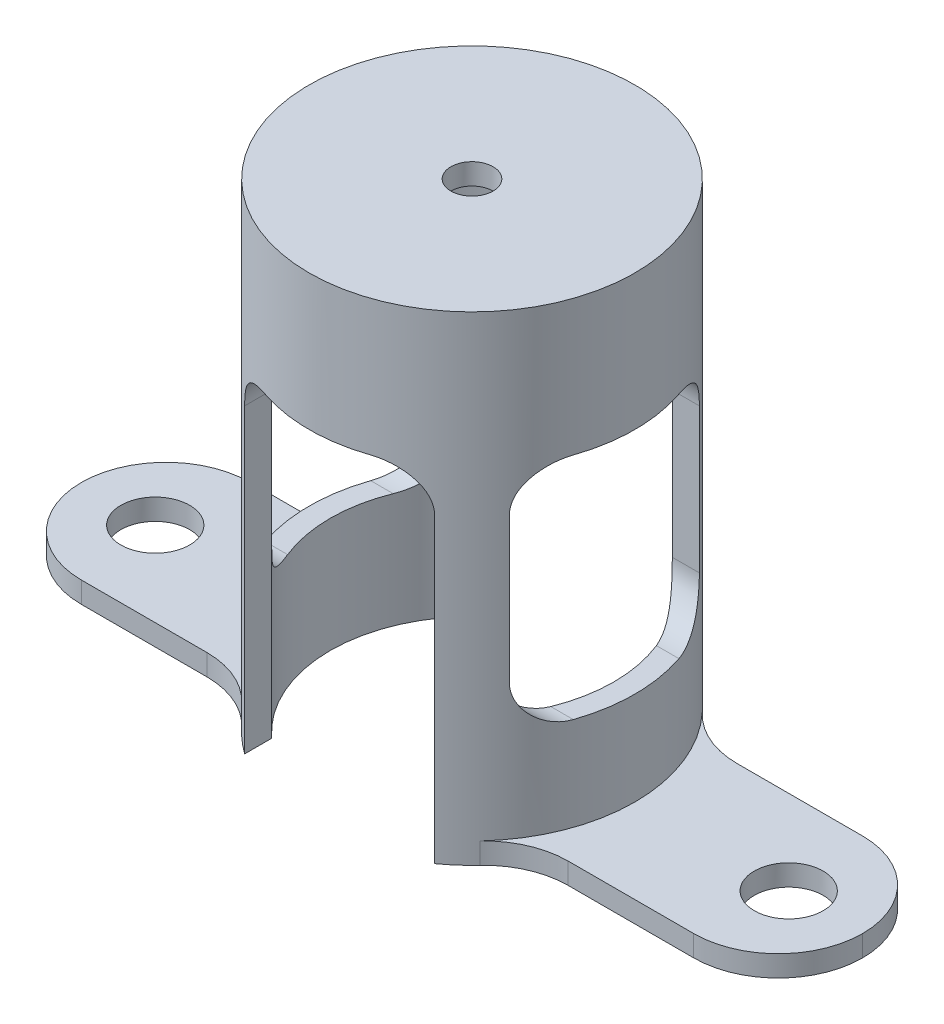
SolidWorks part; units mm, degrees
material "6061-T6 (SS)"
ref_plane "Front Plane" through (0, 0, 0) normal (0, 0, 1) x (1, 0, 0)
ref_plane "Top Plane" through (0, 0, 0) normal (0, 1, 0) x (1, 0, 0)
ref_plane "Right Plane" through (0, 0, 0) normal (1, 0, 0) x (0, 0, -1)
sketch "Sketch2" plane through (0, 0, 0) normal (0, 1, 0) x (1, 0, 0)
  circle A1 centre (0, 0) radius 7.715
  dimension "D2" = 15.43
extrude "Boss-Extrude1" add sketch "Sketch2" along normal blind 21.7
sketch "Sketch4" plane through (0, 21.7, 0) normal (0, 1, 0) x (1, 0, 0)
  circle A0 centre (0, 0) radius 1
  dimension "D1" = 2
extrude "Cut-Extrude2" cut sketch "Sketch4" against normal through all
sketch "Sketch11" plane through (0, 0, 0) normal (0, -1, 0) x (1, 0, 0)
  line L0 (6.5971, 4) -> (18.5, 4)
  line L1 (-18.5, 4) -> (-6.5971, 4)
  line L2 (-18.5, 4) -> (-18.5, -4)
  line L3 (-18.5, -4) -> (-6.5971, -4)
  line L4 (18.5, 4) -> (18.5, -4)
  line L5 (-18.5, 4) -> (18.5, -4) construction
  line L6 (-18.5, -4) -> (18.5, 4) construction
  line L7 (6.5971, -4) -> (18.5, -4)
  arc A0 (6.5971, 4) -> (-6.5971, 4) centre (0, 0) ccw
  circle A1 centre (0, 0) radius 6.715
  arc A2 (-6.5971, -4) -> (6.5971, -4) centre (0, 0) ccw
  point P0 (0, 0)
  dimension "D3" = 15.43
  dimension "D4" = 13.43
  dimension "D1" = 8
  dimension "D2" = 37
extrude "Boss-Extrude2" add sketch "Sketch11" along normal blind 1
sketch "Sketch12" plane through (0, 0, 0) normal (0, -1, 0) x (1, 0, 0)
  circle A0 centre (0, 0) radius 6.715
  dimension "D1" = 13.43
extrude "Cut-Extrude7" cut sketch "Sketch12" against normal blind 20.7
ref_plane "Plane4" through (0, 0, 30) normal (0, 0, 1) x (1, 0, 0)
sketch "Sketch13" plane through (0, 0, 30) normal (0, 0, 1) x (1, 0, 0)
  line L0 (0, -8.4865) -> (0, 8.4865) construction
  line L1 (-4.5, 15.275) -> (4.5, 15.275)
  line L2 (-4.5, 15.275) -> (-4.5, -1)
  line L3 (-4.5, -1) -> (4.5, -1)
  line L4 (4.5, 15.275) -> (4.5, -1)
  line L5 (-4.5, 15.275) -> (4.5, -1) construction
  line L6 (-4.5, -1) -> (4.5, 15.275) construction
  line L7 (-6.5971, -1) -> (6.5971, -1) construction
  point P0 (0, 7.1375)
  dimension "D1" = 16.275
  dimension "D2" = 9
extrude "Cut-Extrude8" cut sketch "Sketch13" against normal through all
ref_plane "Plane5" through (30, 0, 0) normal (1, 0, 0) x (0, 0, -1)
sketch "Sketch14" plane through (30, 0, 0) normal (1, 0, 0) x (0, 0, -1)
  line L0 (0, 13.585) -> (0, -13.585) construction
  line L1 (-4.5, 15.275) -> (4.5, 15.275)
  line L2 (-4.5, 15.275) -> (-4.5, 4.425)
  line L3 (-4.5, 4.425) -> (4.5, 4.425)
  line L4 (4.5, 15.275) -> (4.5, 4.425)
  line L5 (-4.5, 15.275) -> (4.5, 4.425) construction
  line L6 (-4.5, 4.425) -> (4.5, 15.275) construction
  line L7 (4, -1) -> (-4, -1) construction
  point P0 (0, 9.85)
  dimension "D2" = 9
  dimension "D1" = 10.85
  dimension "D3" = 10.85
extrude "Cut-Extrude9" cut sketch "Sketch14" against normal through all
fillet "Fillet3" radius 2 12 edges at (4.5, 15.275, -5.6254) (-4.5, 15.275, -5.6254) (-4.5, 15.275, 5.6254) (4.5, 15.275, 5.6254) (-5.6254, 15.275, 4.5) (-5.6254, 15.275, -4.5) (-5.6254, 4.425, -4.5) (-5.6254, 4.425, 4.5) (5.6254, 4.425, 4.5) (5.6254, 15.275, 4.5) (5.6254, 15.275, -4.5) (5.6254, 4.425, -4.5)
fillet "Fillet4" radius 4 8 edges at (6.5971, -0.5, -4) (18.5, -0.5, -4) (6.5971, -0.5, 4) (18.5, -0.5, 4) (-6.5971, -0.5, 4) (-18.5, -0.5, -4) (-6.5971, -0.5, -4) (-18.5, -0.5, 4)
sketch "Sketch15" plane through (0, 0, 0) normal (0, 1, 0) x (1, 0, 0)
  line L0 (-13.585, 0) -> (13.585, 0) construction
  circle A0 centre (-15, 0) radius 1.63
  circle A1 centre (15, 0) radius 1.63
  dimension "D3" = 3.26
  dimension "D4" = 3.26
  dimension "D1" = 15
extrude "Cut-Extrude10" cut sketch "Sketch15" against normal up to next
equation "\"FrangiboltTotalDiameter\" = .450in"
equation "\"FrangiboltTotalLength\" = .500in"
equation "\"FrangiboltThruHoleDiameter\"= .116in"
equation "\"EnclosureWallThickness\"= 1mm"
equation "\"EnclosureWallSpacing\"= 1mm"
equation "\"EnclosureInnerDiameter\"= \"FrangiboltTotalDiameter\" + 2 * \"EnclosureWallSpacing\""
equation "\"EnclosureOuterDiameter\"= \"FrangiboltTotalDiameter\" + 2 * \"EnclosureWallSpacing\" + 2 * \"EnclosureWallThickness\""
equation "\"EnclosureTotalLength\"= \"FrangiboltTotalLength\" + \"DamperLength\" + \"EnclosureWallThickness\""
equation "\"D2@Sketch2\"=\"EnclosureOuterDiameter\""
equation "\"D1@Boss-Extrude1\"=\"EnclosureTotalLength\""
equation "\"DamperLength\"= 8"
equation "\"EnclosureLip\"= 5mm"
equation "\"FrangiboltBoxWidth\"= 7mm"
equation "\"EnclosureMountingStandoff\"= 37mm"
equation "\"D2@Sketch11\"=\"EnclosureMountingStandoff\""
equation "\"D3@Sketch11\"=\"EnclosureOuterDiameter\""
equation "\"D4@Sketch11\"=\"EnclosureInnerDiameter\""
equation "\"D1@Boss-Extrude2\"=\"EnclosureWallThickness\""
equation "\"D1@Sketch12\"=\"EnclosureInnerDiameter\""
equation "\"D1@Cut-Extrude7\"=\"EnclosureTotalLength\"-\"EnclosureWallThickness\""
equation "\"D1@Sketch13\"=\"EnclosureTotalLength\"*0.75"
equation "\"D2@Sketch13\"=\"FrangiboltBoxWidth\"+2mm"
equation "\"D1@Sketch14\"=\"EnclosureTotalLength\"*0.5"
equation "\"D2@Sketch14\"=\"FrangiboltBoxWidth\"+2mm"
equation "\"D3@Sketch14\"=\"EnclosureTotalLength\"*0.5"
equation "\"EnclosureMountingHoleDiameter\"= 3.26mm"
equation "\"D3@Sketch15\"=\"EnclosureMountingHoleDiameter\""
equation "\"D4@Sketch15\"=\"EnclosureMountingHoleDiameter\""
